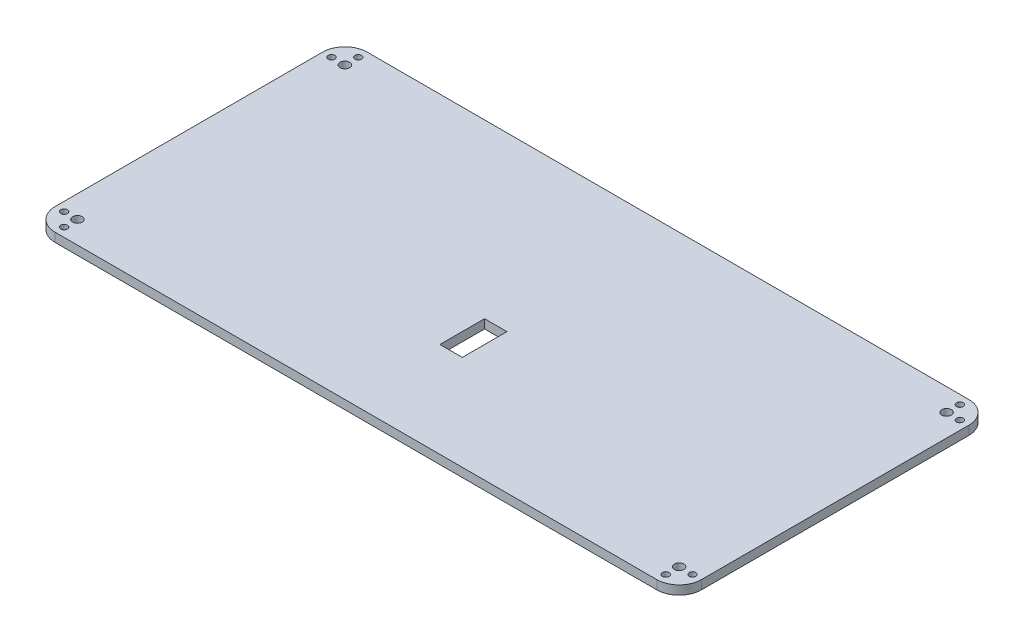
SolidWorks part; units mm, degrees
ref_plane "Front Plane" through (0, 0, 0) normal (0, 0, 1) x (1, 0, 0)
ref_plane "Top Plane" through (0, 0, 0) normal (0, 1, 0) x (1, 0, 0)
ref_plane "Right Plane" through (0, 0, 0) normal (1, 0, 0) x (0, 0, -1)
sketch "Sketch1" plane through (0, 0, 0) normal (0, 1, 0) x (1, 0, 0)
  line L0 (0, 0) -> (145, 0) construction
  line L1 (145, 0) -> (145, -60)
  line L2 (135, -70) -> (0, -70)
  line L3 (0, -70) -> (0, 0)
  line L4 (0, 0) -> (145, 0)
  line L5 (135, -60) -> (141, -60) construction
  line L6 (135, -60) -> (145, -70) construction
  arc A0 (135, -70) -> (145, -60) centre (135, -60) ccw
  arc A1 (135, -57.85) -> (137.15, -60) centre (135, -60) ccw
  circle A2 centre (135, -60) radius 2.15
  circle A3 centre (141, -60) radius 1.5
  circle A4 centre (135, -66) radius 1.5
  point P7 (145, -70)
  point P17 (145, -70)
  dimension "D4" = 10
  dimension "D5" = 4.3
  dimension "D7" = 3
  dimension "D1" = 145
  dimension "D2" = 70
  dimension "D3" = 145
  dimension "D6" = 6
extrude "Boss-Extrude1" add sketch "Sketch1" along normal blind 4 contours L2 A0 L1 L4 L3 A1 region at (72.1692, 0, 34.8552)
mirror "Mirror1" about plane through (0, 0, 0) normal (1, 0, 0) of "Boss-Extrude1"
mirror "Mirror2" about plane through (0, 0, 0) normal (0, 0, 1) of "Mirror1"
sketch "Sketch2" plane through (0, 4, 0) normal (0, 1, 0) x (1, 0, 0)
  line L7 (-5.05, -26.8091) -> (-5.05, -27.3091) construction
  line L9 (4.5, -7.2591) -> (5, -7.2591) construction
  line L11 (-5.05, -27.3091) -> (5, -27.3091)
  line L12 (-5.05, -27.3091) -> (-5.05, -7.2591)
  line L13 (-5.05, -7.2591) -> (5, -7.2591)
  line L14 (5, -27.3091) -> (5, -7.2591)
  dimension "D2" = 0.5
  dimension "D4" = 0.5
extrude "Cut-Extrude5" cut sketch "Sketch2" against normal through all
